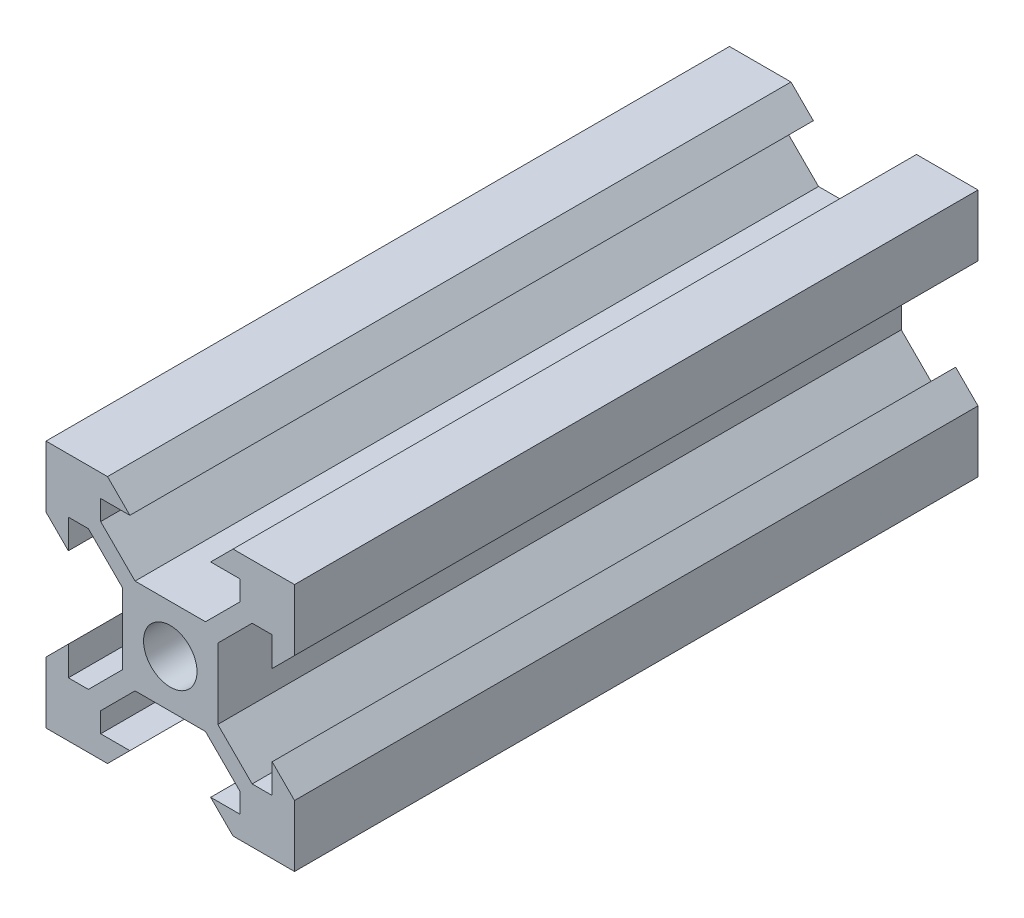
SolidWorks part; units mm, degrees
ref_plane "Alzado" through (0, 0, 0) normal (0, 0, 1) x (1, 0, 0)
ref_plane "Planta" through (0, 0, 0) normal (0, 1, 0) x (1, 0, 0)
ref_plane "Vista lateral" through (0, 0, 0) normal (1, 0, 0) x (0, 0, -1)
sketch "Croquis1" plane through (0, 0, 0) normal (0, 0, 1) x (1, 0, 0)
  line L0 (0, 0) -> (0, -20) construction
  line L2 (0, 0) -> (0, -0.5674)
  line L5 (6.175, -7.1649) -> (6.175, -12.8351)
  line L6 (7.1649, -13.825) -> (12.8351, -13.825)
  line L7 (13.825, -7.1649) -> (13.825, -12.8351)
  line L8 (7.1649, -6.175) -> (12.8351, -6.175)
  line L9 (6.175, -13.825) -> (13.825, -13.825) construction
  line L10 (13.825, -6.175) -> (13.825, -13.825) construction
  line L12 (10, -10) -> (32.1172, -10) construction
  line L13 (13.25, -18.2) -> (15.05, -20)
  line L14 (20, -20) -> (15.6, -20)
  line L15 (20, -20) -> (20, -15.6)
  line L16 (18.2, -15.6) -> (16.5899, -15.6)
  line L32 (15.6, -18.2) -> (15.6, -16.5899)
  line L33 (10, -10) -> (10, -23.2493) construction
  line L34 (4.4, -18.2) -> (4.4, -16.5899)
  line L35 (7.1649, -13.825) -> (4.4, -16.5899)
  line L36 (15.6, -18.2) -> (13.25, -18.2)
  line L38 (15.6, -20) -> (15.05, -20)
  line L40 (15.05, -20) -> (20, -20)
  line L41 (0, -20) -> (20, -20) construction
  line L42 (6.175, -12.8351) -> (3.4101, -15.6)
  line L43 (18.2, -13.25) -> (20, -15.05)
  line L44 (20, -20) -> (18.2, -20)
  line L45 (20, -20) -> (20, -15.05)
  line L48 (20, -15.05) -> (20, -20)
  line L49 (20, 0) -> (20, -20) construction
  line L50 (18.2, -15.6) -> (18.2, -13.25)
  line L51 (12.8351, -13.825) -> (15.6, -16.5899)
  line L52 (13.825, -12.8351) -> (16.5899, -15.6)
  line L53 (1.8, -15.6) -> (3.4101, -15.6)
  line L54 (1.8, -15.6) -> (1.8, -13.25)
  line L55 (1.8, -13.25) -> (0, -15.05)
  line L56 (0, 0) -> (20, 0) construction
  line L57 (0, -20) -> (0, -15.6)
  line L58 (0, -15.6) -> (0, -15.05)
  line L59 (0, -20) -> (4.4, -20)
  line L60 (0, -20) -> (4.95, -20)
  line L61 (6.75, -18.2) -> (4.95, -20)
  line L62 (4.4, -18.2) -> (6.75, -18.2)
  line L63 (1.8, -4.4) -> (3.4101, -4.4)
  line L64 (6.175, -7.1649) -> (3.4101, -4.4)
  line L65 (7.1649, -6.175) -> (4.4, -3.4101)
  line L66 (4.4, -1.8) -> (4.4, -3.4101)
  line L67 (4.4, -1.8) -> (6.75, -1.8)
  line L68 (6.75, -1.8) -> (4.95, 0)
  line L69 (0, 0) -> (4.4, 0)
  line L70 (4.4, 0) -> (4.95, 0)
  line L71 (0, 0) -> (0, -4.4)
  line L72 (0, 0) -> (0, -4.95)
  line L73 (1.8, -6.75) -> (0, -4.95)
  line L74 (1.8, -4.4) -> (1.8, -6.75)
  line L75 (15.6, -1.8) -> (15.6, -3.4101)
  line L76 (12.8351, -6.175) -> (15.6, -3.4101)
  line L77 (13.825, -7.1649) -> (16.5899, -4.4)
  line L78 (18.2, -4.4) -> (16.5899, -4.4)
  line L79 (18.2, -4.4) -> (18.2, -6.75)
  line L80 (18.2, -6.75) -> (20, -4.95)
  line L81 (20, 0) -> (20, -4.4)
  line L82 (20, -4.4) -> (20, -4.95)
  line L83 (20, 0) -> (15.6, 0)
  line L84 (20, 0) -> (15.05, 0)
  line L85 (13.25, -1.8) -> (15.05, 0)
  line L86 (15.6, -1.8) -> (13.25, -1.8)
  line L87 (6.175, -6.175) -> (13.825, -6.175) construction
  line L88 (6.175, -6.175) -> (6.175, -13.825) construction
  circle A0 centre (10, -10) radius 2.15
  point P69 (10, -10)
  dimension "D3" = 4.3
  dimension "D2" = 4
  dimension "D11" = 4.4
  dimension "D15" = 4.4
  dimension "D16" = 6.75
extrude "Saliente-Extruir2" add sketch "Croquis1" along normal blind 55 contours L86 L75 L76 L8 L65 L66 L67 L68 L70 L69 L2 L71 L72 L73 L74 L63 L64 L5 L42 L53 L54 L55 L58 L57 L59 L60 L61 L62 L34 L35 L6 L51 L32 L36 L13 L38 L40 L14 L15 L45 L43 L50 L16 L52 L7 L77 L78 L79 L80 L82 L81 region at (2.2, -0.2828, 0)
